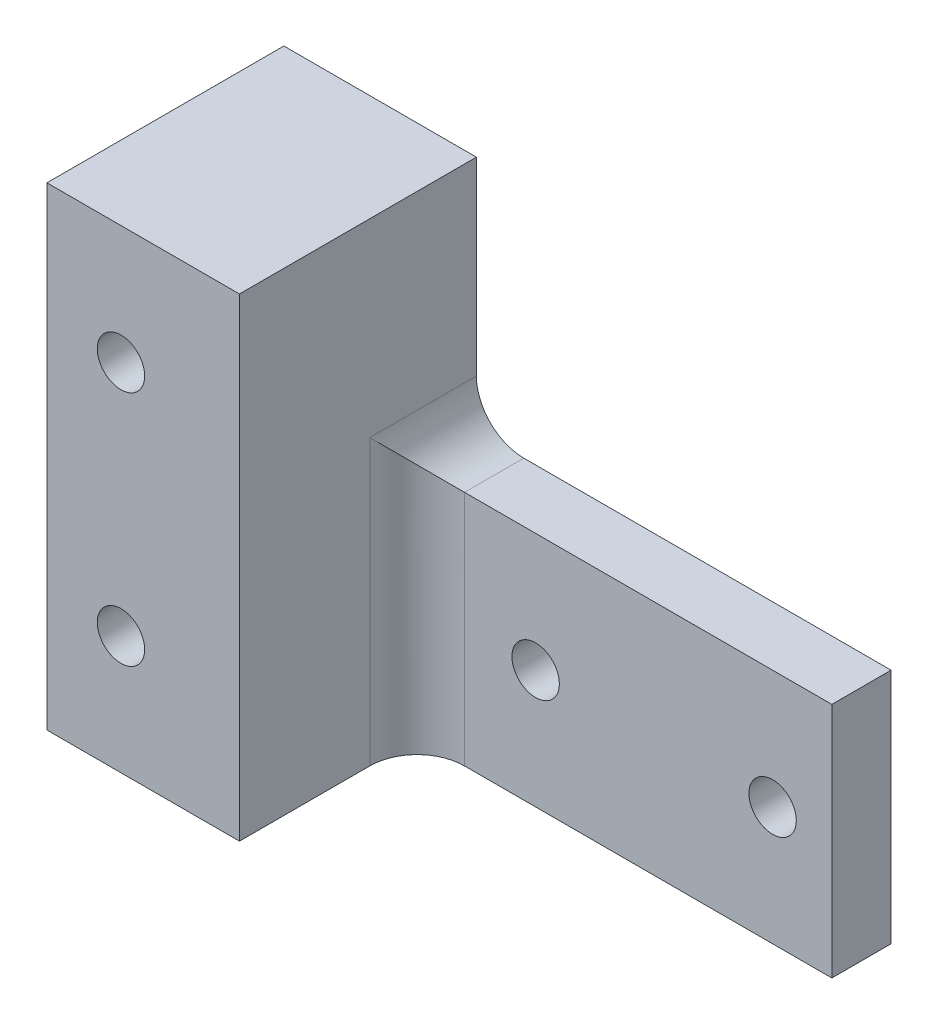
SolidWorks part; units mm, degrees
ref_plane "Front Plane" through (0, 0, 0) normal (0, 0, 1) x (1, 0, 0)
ref_plane "Top Plane" through (0, 0, 0) normal (0, 1, 0) x (1, 0, 0)
ref_plane "Right Plane" through (0, 0, 0) normal (1, 0, 0) x (0, 0, -1)
sketch "Sketch1" plane through (0, 0, 0) normal (0, 0, 1) x (1, 0, 0)
  line L0 (0, 0) -> (0, 50.8)
  line L1 (0, 50.8) -> (25.4, 50.8)
  line L2 (25.4, 50.8) -> (25.4, 25.4)
  line L3 (25.4, 25.4) -> (69.85, 25.4)
  line L4 (69.85, 25.4) -> (69.85, 0)
  line L5 (69.85, 0) -> (0, 0)
  dimension "D1" = 50.8
  dimension "D2" = 25.4
  dimension "3" = 69.85
extrude "Boss-Extrude1" add sketch "Sketch1" along normal blind 25.4
sketch "Sketch2" plane through (0, 0, 25.4) normal (0, 0, 1) x (1, 0, 0)
  line L0 (25.4, 50.8) -> (0, 50.8) construction
  line L1 (25.4, 25.4) -> (25.4, 50.8) construction
  line L2 (0, 0) -> (69.85, 0) construction
  circle A0 centre (12.7, 38.1) radius 2.54
  circle A1 centre (12.7, 12.7) radius 2.54
  circle A2 centre (38.1, 12.7) radius 2.54
  circle A3 centre (63.5, 12.7) radius 2.54
  dimension "D1" = 5.08
  dimension "D2" = 12.7
  dimension "D3" = 12.7
  dimension "D4" = 12.7
  dimension "D5" = 3
extrude "Cut-Extrude1" cut sketch "Sketch2" against normal through all
sketch "Sketch3" plane through (0, 0, 25.4) normal (0, 0, 1) x (1, 0, 0)
  line L0 (25.4, 50.8) -> (0, 50.8) construction
  line L1 (0, 0) -> (4.7625, 0)
  line L2 (0, 0) -> (0, 50.8)
  line L3 (0, 50.8) -> (4.7625, 50.8)
  line L4 (4.7625, 0) -> (4.7625, 50.8)
  dimension "D1" = 4.7625
extrude "Cut-Extrude2" cut sketch "Sketch3" against normal through all
sketch "Sketch4" plane through (0, 0, 0) normal (0, -1, 0) x (1, 0, 0)
  line L5 (69.85, 25.4) -> (25.4, 25.4)
  line L6 (69.85, 25.4) -> (69.85, 6.35)
  line L7 (69.85, 6.35) -> (25.4, 6.35)
  line L8 (25.4, 25.4) -> (25.4, 6.35)
  dimension "D1" = 19.05
  dimension "D2" = 44.45
extrude "Cut-Extrude3" cut sketch "Sketch4" against normal through all
fillet "Fillet1" radius 5.08 2 edges at (25.4, 25.4, 3.175) (25.4, 12.7, 6.35)
sketch "Sketch6" plane through (0, 0, 0) normal (0, 0, -1) x (-1, 0, 0)
  circle A0 centre (-12.7, 38.1) radius 6.35
  dimension "D1" = 12.7
extrude "Cut-Extrude5" cut sketch "Sketch6" against normal blind 12.7
